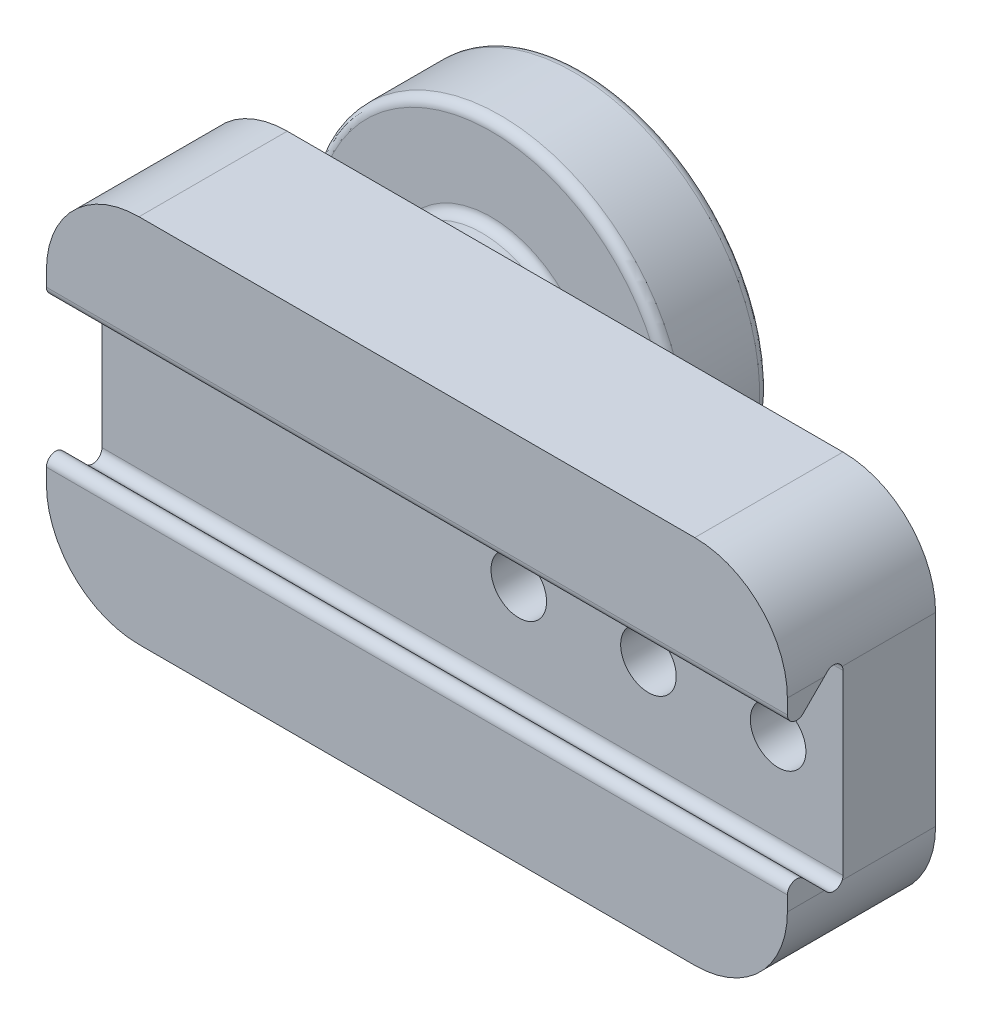
SolidWorks part; units mm, degrees
ref_plane "Front" through (0, 0, 0) normal (0, 0, 1) x (1, 0, 0)
ref_plane "Top" through (0, 0, 0) normal (0, 1, 0) x (1, 0, 0)
ref_plane "Right" through (0, 0, 0) normal (1, 0, 0) x (0, 0, -1)
sketch "Sketch1" plane through (0, 0, 0) normal (0, 0, 1) x (1, 0, 0)
  line L0 (18.3647, 0) -> (-19.4746, 0) construction
  arc A1 (10, 0) -> (-10, 0) centre (0, 0) ccw
  arc A2 (10, 0) -> (-10, 0) centre (0, 0) cw
  point P4 (0, -2.5)
  dimension "D2" = 10
extrude "Boss-Extrude1" add sketch "Sketch1" along normal blind 5
sketch "Sketch2" plane through (0, 0, 0) normal (0, 0, 1) x (1, 0, 0)
  circle A0 centre (0, 0) radius 5
  dimension "D1" = 10
extrude "Boss-Extrude2" add sketch "Sketch2" along normal blind 11
ref_plane "Plane1" through (0, 0, 11) normal (0, 0, 1) x (1, 0, 0)
ref_point "Point1"
sketch "Sketch3" plane through (0, 0, 11) normal (0, 0, 1) x (1, 0, 0)
  line L0 (10, -10) -> (30, -10)
  line L1 (-10, 10) -> (10, 10)
  line L2 (-10, 10) -> (-10, -10)
  line L3 (-10, -10) -> (10, -10)
  line L5 (-10, 10) -> (10, -10) construction
  line L6 (-10, -10) -> (10, 10) construction
  line L7 (30, -10) -> (30, 10)
  line L8 (30, 10) -> (10, 10)
  point P0 (0, 0)
  dimension "D1" = 20
  dimension "D2" = 20
  dimension "D3" = 20
  dimension "D4" = 20
  dimension "D5" = 20
  dimension "D6" = 20
extrude "Boss-Extrude3" add sketch "Sketch3" along normal blind 8
ref_plane "Plane2" through (-10, 0, 0) normal (1, 0, 0) x (0, 0, -1)
sketch "Sketch5" plane through (-10, 0, 0) normal (1, 0, 0) x (0, 0, -1)
  line L0 (-19, 3) -> (-16, 6)
  line L1 (-19, -10) -> (-19, 10) construction
  line L2 (-16, 6) -> (-16, -6)
  line L3 (-16, -6) -> (-19, -3)
  line L4 (-19, -3) -> (-19, 3)
  line L5 (-19, 0) -> (-16, 0) construction
  line L6 (-19, 10) -> (-11, 10) construction
  line L7 (-19, 10) -> (-19, -10) construction
  dimension "D1" = 12
  dimension "D2" = 6
  dimension "D3" = 3
  dimension "D4" = 6
  dimension "D5" = 3
  dimension "D6" = 3
  dimension "D7" = 10
  dimension "D8" = 45
extrude "Cut-Extrude1" cut sketch "Sketch5" along normal blind 42
sketch "Sketch6" plane through (0, 0, 0) normal (0, 0, 1) x (1, 0, 0)
  line L0 (30, 10) -> (-10, 10) construction
  line L2 (30, -6) -> (30, 6) construction
  circle A0 centre (26.5, 0) radius 1.5
  point P6 (30.6839, -2.3373)
  dimension "D1" = 3
  dimension "D2" = 10
  dimension "D3" = 3.5
extrude "Cut-Extrude2" cut sketch "Sketch6" along normal blind 32
pattern_linear "LPattern1" count 3 spacing 7 along (-1, 0, 0) of "Cut-Extrude2"
fillet "Fillet1" radius 0.5 4 edges at (10, -6, 16) (10, -3, 19) (10, 6, 16) (10, 3, 19)
fillet "Fillet2" radius 5 4 edges at (30, -10, 15) (-10, -10, 15) (-10, 10, 15) (30, 10, 15)
fillet "Fillet3" radius 0.5 4 edges at (10, 0, 0) (-10, 0, 5) (-5, 0, 5) (5, 0, 11)
